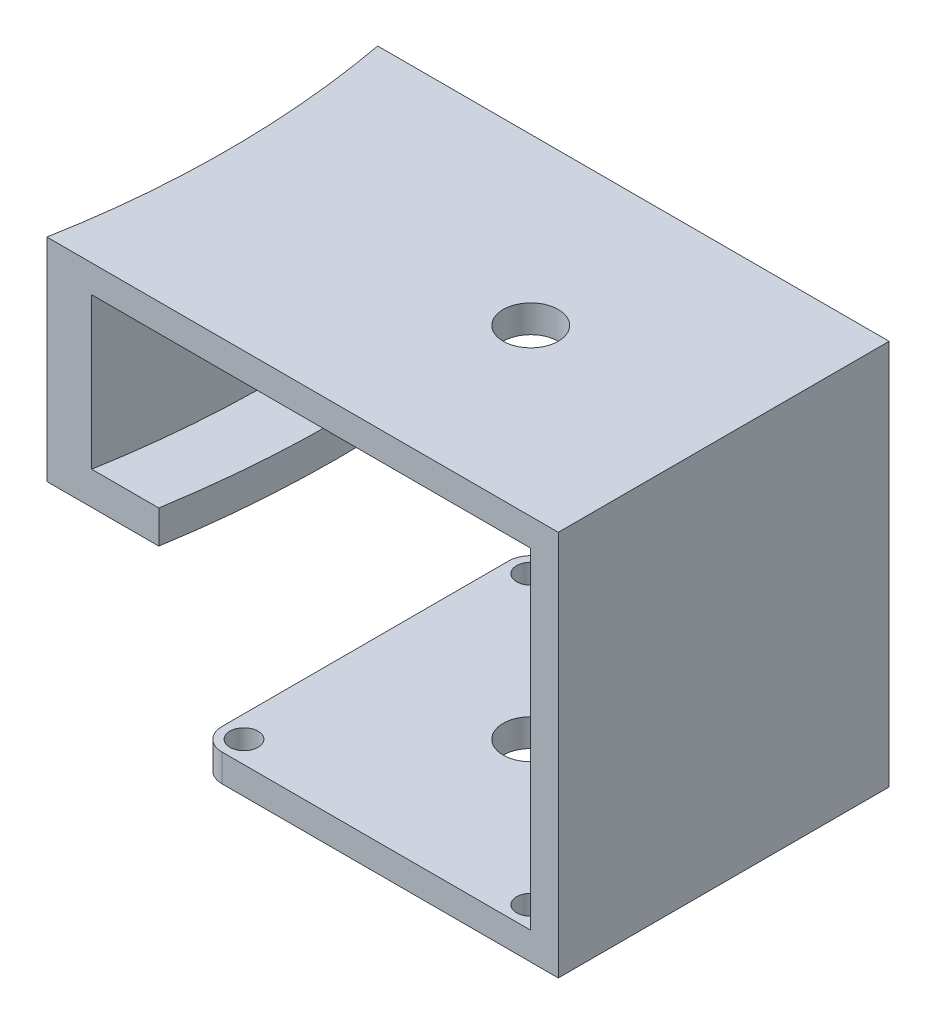
SolidWorks part; units mm, degrees
ref_plane "Front Plane" through (0, 0, 0) normal (0, 0, 1) x (1, 0, 0)
ref_plane "Top Plane" through (0, 0, 0) normal (0, 1, 0) x (1, 0, 0)
ref_plane "Right Plane" through (0, 0, 0) normal (1, 0, 0) x (0, 0, -1)
sketch "Sketch1" plane through (0, 0, 0) normal (0, 1, 0) x (1, 0, 0)
  line L1 (-26, -30) -> (30, -30)
  line L2 (-30, -26) -> (-30, 26)
  line L3 (-26, 30) -> (30, 30)
  line L4 (30, -30) -> (30, 30)
  line L5 (-30, -30) -> (30, 30) construction
  line L6 (-30, 30) -> (30, -30) construction
  arc A1 (-26, -30) -> (-30, -26) centre (-26, -26) cw
  arc A2 (-30, 26) -> (-26, 30) centre (-26, 26) cw
  circle A4 centre (26, 26) radius 2.55
  circle A5 centre (-26, 26) radius 2.55
  circle A6 centre (-26, -26) radius 2.55
  circle A7 centre (26, -26) radius 2.55
  point P0 (0, 0)
  dimension "D4" = 5.1
  dimension "D5" = 5.1
  dimension "D6" = 5.1
  dimension "D7" = 5.1
  dimension "D1" = 60
  dimension "D2" = 60
extrude "Boss-Extrude1" add sketch "Sketch1" along normal blind 5
sketch "Sketch2" plane through (0, 5, 0) normal (0, 1, 0) x (1, 0, 0)
  circle A0 centre (0, 0) radius 5
  dimension "D1" = 10
extrude "Cut-Extrude1" cut sketch "Sketch2" against normal blind 10
sketch "Sketch3" plane through (0, 0, 0) normal (0, -1, 0) x (1, 0, 0)
  line L0 (-26, 30) -> (30, 30) construction
  line L1 (30, -30) -> (35, -30)
  line L2 (30, -30) -> (30, 30)
  line L3 (30, 30) -> (35, 30)
  line L4 (35, -30) -> (35, 30)
  dimension "D1" = 5
extrude "Boss-Extrude2" add sketch "Sketch3" against normal blind 70
sketch "Sketch4" plane through (0, 70, 0) normal (0, 1, 0) x (1, 0, 0)
  line L3 (30, -30) -> (30, 30) construction
  line L7 (30, -30) -> (30, 30)
  line L8 (30, 30) -> (-50, 30)
  line L9 (-50, 30) -> (-50, -30)
  line L10 (-50, -30) -> (30, -30)
  dimension "D1" = 80
sketch "Sketch5" plane through (0, 70, 0) normal (0, 1, 0) x (1, 0, 0)
  circle A0 centre (0, 0) radius 5
  dimension "D1" = 10
extrude "Boss-Extrude4" add sketch "Sketch4" against normal blind 5
extrude "Cut-Extrude3" cut sketch "Sketch5" against normal blind 5
sketch "Sketch7" plane through (0, 0, 0) normal (0, 1, 0) x (1, 0, 0)
  line L0 (35, 30) -> (35, -30) construction
  circle A0 centre (-220, 0) radius 255
  circle A1 centre (-220, 0) radius 185
  circle A2 centre (-220, 0) radius 175
  dimension "D1" = 510
  dimension "D2" = 350
  dimension "D3" = 370
sketch "Sketch8" plane through (0, 0, 0) normal (0, 1, 0) x (1, 0, 0)
  circle A2 centre (-220, 0) radius 165
  circle A3 centre (-220, 0) radius 165
  dimension "D1" = 10
sketch "Sketch9" plane through (0, 0, 0) normal (0, 1, 0) x (1, 0, 0)
  line L0 (-37.4486, 30) -> (-57.7502, 30)
  line L1 (-50, 30) -> (35, 30) construction
  line L2 (-37.4486, -30) -> (-57.7502, -30)
  line L3 (35, -30) -> (-50, -30) construction
  circle A0 centre (-220, 0) radius 165 construction
  circle A1 centre (-220, 0) radius 185 construction
  circle A2 centre (-220, 0) radius 175 construction
  arc A3 (-37.4486, -30) -> (-37.4486, 30) centre (-220, 0) ccw
  arc A4 (-47.5906, -30) -> (-47.5906, 30) centre (-220, 0) ccw
  arc A5 (-57.7502, -30) -> (-57.7502, 30) centre (-220, 0) ccw
ref_plane "Plane1" through (0, 31.6, 0) normal (0, 1, 0) x (1, 0, 0)
sketch "Sketch10" plane through (0, 31.6, 0) normal (0, 1, 0) x (1, 0, 0)
  line L0 (-37.4486, -30) -> (-57.7502, -30) construction
  line L1 (-37.4486, 30) -> (-57.7502, 30) construction
  line L2 (-37.4486, -30) -> (-57.7502, -30)
  line L3 (-37.4486, 30) -> (-57.7502, 30)
  arc A0 (-37.4486, -30) -> (-37.4486, 30) centre (-220, 0) ccw construction
  arc A1 (-57.7502, -30) -> (-57.7502, 30) centre (-220, 0) ccw construction
  arc A2 (-37.4486, -30) -> (-37.4486, 30) centre (-220, 0) ccw
  arc A3 (-57.7502, -30) -> (-57.7502, 30) centre (-220, 0) ccw
extrude "Boss-Extrude6" add sketch "Sketch10" along normal blind 6 separate body
sketch "Sketch11" plane through (0, 70, 0) normal (0, 1, 0) x (1, 0, 0)
  line L0 (-37.4486, -30) -> (-57.7502, -30) construction
  line L1 (-37.4486, 30) -> (-57.7502, 30) construction
  line L2 (-49.621, -30) -> (-57.7502, -30)
  line L3 (-49.621, 30) -> (-57.7502, 30)
  line L4 (35, 30) -> (-50, 30)
  line L5 (-50, 30) -> (-50, -30)
  line L6 (-50, -30) -> (35, -30)
  line L7 (35, -30) -> (35, 30)
  line L8 (-49.621, 30) -> (-50, 30)
  line L10 (-50, -30) -> (-49.621, -30)
  line L11 (35, -30) -> (35, 30)
  arc A1 (-57.7502, -30) -> (-57.7502, 30) centre (-220, 0) ccw construction
  arc A3 (-57.7502, -30) -> (-57.7502, 30) centre (-220, 0) ccw
  arc A4 (-49.621, -30) -> (-49.621, 30) centre (-220, 0) ccw
  line M6 (35, 30) -> (-50, 30)
  line M7 (-50, 30) -> (-50, -30)
  line M8 (-50, -30) -> (35, -30)
  dimension "D1" = 0
extrude "Boss-Extrude7" add sketch "Sketch11" against normal up to surface (32.4 mm away) contours A3 L2 L3 M7 | M8 M6 M7 region at (-48.7924, 70, 0) region at (-53.0135, 70, 0) up to face at (-46.2997, 37.6, 0)
